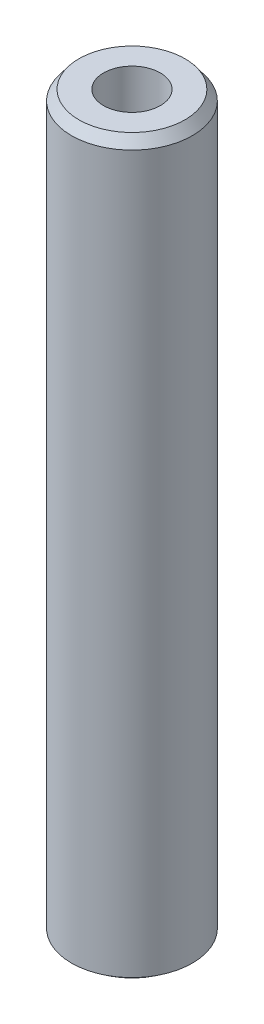
SolidWorks part; units mm, degrees
ref_plane "Front Plane" through (0, 0, 0) normal (0, 0, 1) x (1, 0, 0)
ref_plane "Top Plane" through (0, 0, 0) normal (0, 1, 0) x (1, 0, 0)
ref_plane "Right Plane" through (0, 0, 0) normal (1, 0, 0) x (0, 0, -1)
sketch "Sketch1" plane through (0, 0, 0) normal (0, 1, 0) x (1, 0, 0)
  circle A0 centre (0, 0) radius 25
  dimension "SHAFT_OD" = 50
extrude "Boss-Extrude1" add sketch "Sketch1" along normal blind 303.7623
sketch "Sketch2" plane through (0, 0, 0) normal (0, 1, 0) x (1, 0, 0)
  circle A0 centre (0, 0) radius 11.7458
  dimension "BORE_D" = 23.4916
extrude "Cut-Extrude1" cut sketch "Sketch2" along normal through all
chamfer "Chamfer1" distance 4.1412 angle 36.557 2 edges at (0, 303.7623, 25) (0, 0, 25) first distance on face at (0, 303.7623, 25) first distance on face at (0, 0, 11.7458)
